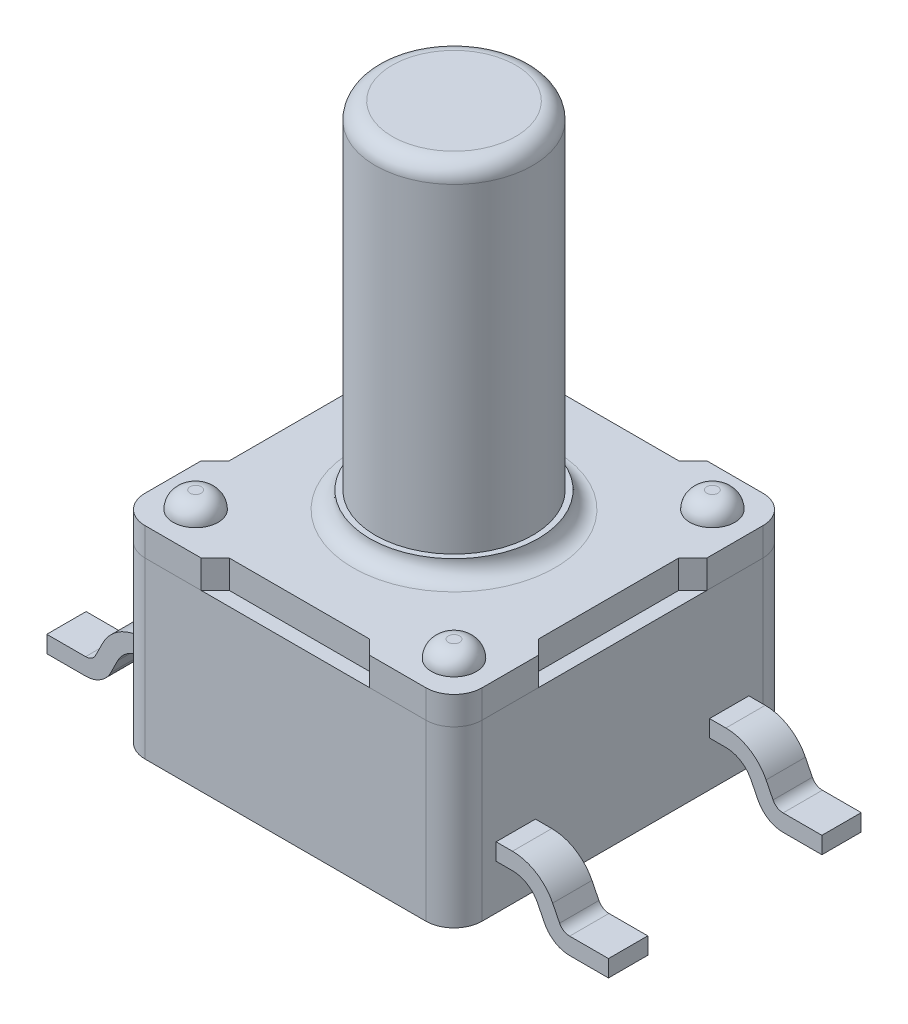
SolidWorks part; units mm, degrees
ref_plane "Front Plane" through (0, 0, 0) normal (0, 0, 1) x (1, 0, 0)
ref_plane "Top Plane" through (0, 0, 0) normal (0, 1, 0) x (1, 0, 0)
ref_plane "Right Plane" through (0, 0, 0) normal (1, 0, 0) x (0, 0, -1)
sketch "Sketch1" plane through (0, 0, 0) normal (0, 1, 0) x (1, 0, 0)
  line L1 (-2.5, -3) -> (2.5, -3)
  line L2 (-3, -2.5) -> (-3, 2.5)
  line L3 (-2.5, 3) -> (2.5, 3)
  line L4 (3, -2.5) -> (3, 2.5)
  line L5 (-3, -3) -> (3, 3) construction
  line L6 (-3, 3) -> (3, -3) construction
  arc A0 (-2.5, -3) -> (-3, -2.5) centre (-2.5, -2.5) cw
  arc A1 (2.5, -3) -> (3, -2.5) centre (2.5, -2.5) ccw
  arc A2 (2.5, 3) -> (3, 2.5) centre (2.5, 2.5) cw
  arc A3 (-3, 2.5) -> (-2.5, 3) centre (-2.5, 2.5) cw
  point P0 (0, 0)
  dimension "D3" = 0.5
  dimension "D1" = 6
  dimension "D2" = 6
extrude "Boss-Extrude1" add sketch "Sketch1" along normal blind 3.1
sketch "Sketch2" plane through (0, 3.1, 0) normal (0, 1, 0) x (1, 0, 0)
  line L0 (2.5, 3) -> (-2.5, 3) construction
  line L1 (-2.5, -3) -> (2.5, -3)
  line L2 (-3, -2.5) -> (-3, 2.5)
  line L3 (-2.5, 3) -> (2.5, 3)
  line L4 (3, -2.5) -> (3, 2.5)
  line L5 (-3, -3) -> (3, 3) construction
  line L6 (-3, 3) -> (3, -3) construction
  arc A0 (-2.5, -3) -> (-3, -2.5) centre (-2.5, -2.5) cw
  arc A1 (2.5, -3) -> (3, -2.5) centre (2.5, -2.5) ccw
  arc A2 (2.5, 3) -> (3, 2.5) centre (2.5, 2.5) cw
  arc A3 (-3, 2.5) -> (-2.5, 3) centre (-2.5, 2.5) cw
  point P0 (0, 0)
  dimension "D2" = 0.5
  dimension "D1" = 6
extrude "Boss-Extrude2" add sketch "Sketch2" along normal blind 0.5 separate body
sketch "Sketch3" plane through (0, 3.6, 0) normal (0, 1, 0) x (1, 0, 0)
  circle A0 centre (-2.3, 2.3) radius 0.4
  circle A1 centre (2.3, 2.3) radius 0.4
  circle A2 centre (2.3, -2.3) radius 0.4
  circle A3 centre (-2.3, -2.3) radius 0.4
  dimension "D5" = 0.8
  dimension "D1" = 2.3
  dimension "D2" = 2.3
  dimension "D6" = 2.3
  dimension "D7" = 2.3
  dimension "D8" = 2.3
  dimension "D9" = 2.3
  dimension "D3" = 2
  dimension "D4" = 2
extrude "Boss-Extrude3" add sketch "Sketch3" along normal blind 0.3 separate body
fillet "Fillet1" radius 0.3 1 edges at (-2.3, 3.9, 2.7)
fillet "Fillet2" radius 0.3 1 edges at (-2.3, 3.9, -1.9)
fillet "Fillet3" radius 0.3 1 edges at (2.3, 3.9, -1.9)
fillet "Fillet4" radius 0.3 1 edges at (2.3, 3.9, 2.7)
sketch "Sketch4" plane through (0, 3.6, 0) normal (0, 1, 0) x (1, 0, 0)
  circle A0 centre (0, 0) radius 1.5
  dimension "D1" = 3
extrude "Boss-Extrude4" add sketch "Sketch4" along normal blind 0.3
sketch "Sketch6" plane through (0, 0, 0) normal (0, 0, 1) x (1, 0, 0)
  line L12 (3, 0.8) -> (3.291, 0.8)
  line L13 (3, 3.1) -> (3, 0) construction
  line L14 (3.7382, 0.5236) -> (3.8618, 0.2764)
  line L15 (4.309, 0) -> (5, 0)
  line L16 (3, 1.1) -> (3.291, 1.1)
  line L17 (4.0065, 0.6578) -> (4.1301, 0.4106)
  line L18 (4.309, 0.3) -> (5, 0.3)
  line L19 (3, 0.8) -> (3, 1.1)
  line L20 (5, 0) -> (5, 0.3)
  arc A8 (3.291, 0.8) -> (3.7382, 0.5236) centre (3.291, 0.3) cw
  arc A9 (3.8618, 0.2764) -> (4.309, 0) centre (4.309, 0.5) ccw
  arc A10 (3.291, 1.1) -> (4.0065, 0.6578) centre (3.291, 0.3) cw
  arc A11 (4.1301, 0.4106) -> (4.309, 0.3) centre (4.309, 0.5) ccw
  point P4 (0, 0)
  point P9 (3.6, 0.8)
  point P12 (4, 0)
  dimension "D5" = 0.5
  dimension "D6" = 0.3
  dimension "D3" = 0.6
  dimension "D1" = 5
  dimension "D2" = 0.8
  dimension "D4" = 1
extrude "Boss-Extrude6" add sketch "Sketch6" against normal blind 0.7 from offset 2.25 separate body
pattern_linear "LPattern1" count 2 spacing 3.8 along (0, 0, -1) of "Boss-Extrude6"
mirror "Mirror5" about plane through (0, 0, 0) normal (1, 0, 0) of "LPattern1", "Boss-Extrude6"
sketch "Sketch7" plane through (0, 3.6, 0) normal (0, 1, 0) x (1, 0, 0)
  line L0 (-1.5, 3) -> (-1.25, 2.75)
  line L1 (2.5, 3) -> (-2.5, 3) construction
  line L2 (-1.25, 2.75) -> (1.25, 2.75)
  line L3 (1.25, 2.75) -> (1.5, 3)
  line L4 (1.5, 3) -> (-1.5, 3)
  line L5 (3, -1.5) -> (3, 1.5)
  line L6 (3, 1.5) -> (2.75, 1.25)
  line L7 (2.75, 1.25) -> (2.75, -1.25)
  line L8 (2.75, -1.25) -> (3, -1.5)
  line L9 (-1.5, -3) -> (1.5, -3)
  line L10 (1.5, -3) -> (1.25, -2.75)
  line L11 (1.25, -2.75) -> (-1.25, -2.75)
  line L12 (-1.25, -2.75) -> (-1.5, -3)
  line L13 (-3, 1.5) -> (-3, -1.5)
  line L14 (-3, -1.5) -> (-2.75, -1.25)
  line L15 (-2.75, -1.25) -> (-2.75, 1.25)
  line L16 (-2.75, 1.25) -> (-3, 1.5)
  point P4 (0, 3)
  point P7 (-3, 0)
  point P9 (0, 0)
  point P10 (3, 0)
  point P23 (0, 0)
  point P24 (0, 0)
  point P25 (0, -3)
  dimension "D1" = 3
  dimension "D2" = 2.5
  dimension "D3" = 0.25
  dimension "D4" = 4
extrude "Cut-Extrude1" cut sketch "Sketch7" against normal up to next (0.5 mm away)
fillet "Fillet8" radius 0.3 1 edges at (0, 3.6, 1.5)
sketch "Sketch10" plane through (0, 3.9, 0) normal (0, 1, 0) x (1, 0, 0)
  circle A0 centre (0, 0) radius 1.4
  dimension "D1" = 2.8
extrude "Boss-Extrude10" add sketch "Sketch10" along normal blind 6 separate body
fillet "Fillet9" radius 0.3 1 edges at (0, 9.9, 1.4)
